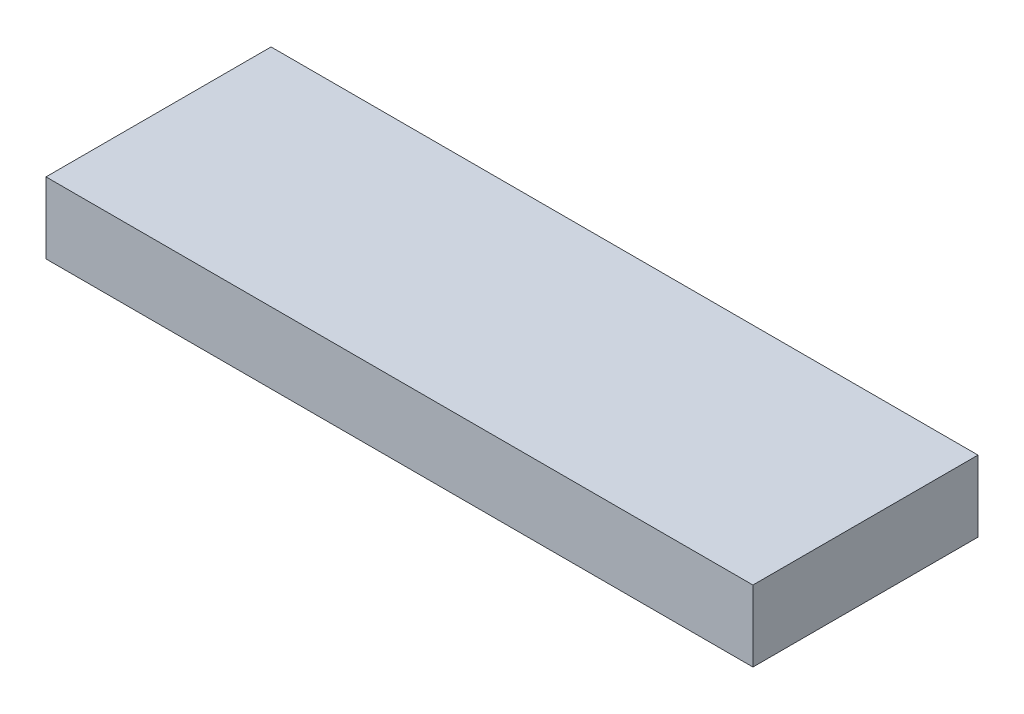
SolidWorks part; units mm, degrees
material "MDF"
ref_plane "Front Plane" through (0, 0, 0) normal (0, 0, 1) x (1, 0, 0)
ref_plane "Top Plane" through (0, 0, 0) normal (0, 1, 0) x (1, 0, 0)
ref_plane "Right Plane" through (0, 0, 0) normal (1, 0, 0) x (0, 0, -1)
sketch "Sketch1" plane through (0, 0, 0) normal (0, 0, 1) x (1, 0, 0)
  line L1 (133.8612, 0) -> (323.3388, 0)
  line L2 (133.8612, 0) -> (133.8612, -19.05)
  line L3 (133.8612, -19.05) -> (323.3388, -19.05)
  line L4 (323.3388, 0) -> (323.3388, -19.05)
  line L5 (323.3388, -298.45) -> (323.3388, 20.8246) construction
  line L6 (133.8612, -298.45) -> (133.8612, 20.8246) construction
  line L8 (456.6888, 0) -> (0.5112, 0) construction
  dimension "D1" = 19.05
extrude "Boss-Extrude1" add sketch "Sketch1" along normal up to surface (60.325 mm away)
hole_wizard "Hole1" positions "Sketch2" profile "Sketch3" legacy
sketch "Sketch2" plane through (228.6, 0, -25.4) normal (0, 0, -1) x (-1, 0, 0)
  line L0 (218.5638, 0) -> (218.5638, -437.642) construction
  line L4 (104.2638, 0) -> (104.2638, -298.45) construction
  line L13 (120.1388, -460.375) -> (120.1388, -311.15) construction
  line L16 (126.4888, -311.15) -> (113.7888, -311.15) construction
  line L18 (126.4888, -304.8) -> (-126.4888, -304.8) construction
  line L22 (94.7388, -276.225) -> (-94.7388, -276.225) construction
  line L24 (-94.7388, -285.75) -> (-94.7388, -266.7) construction
  line L26 (94.7388, -285.75) -> (94.7388, -266.7) construction
  line L27 (-94.7388, 0) -> (-94.7388, -19.05) construction
  line L29 (94.7388, 0) -> (94.7388, -19.05) construction
  line L31 (94.7388, -9.525) -> (-94.7388, -9.525) construction
  point P15 (218.5638, -31.75)
  point P17 (218.5638, -218.821)
  point P19 (218.5638, -418.592)
  point P28 (104.2638, -19.05)
  point P30 (104.2638, -149.225)
  point P32 (104.2638, -279.4)
  point P69 (120.1388, -330.2)
  point P71 (120.1388, -441.325)
  point P76 (-120.1388, -441.325)
  point P77 (-120.1388, -330.2)
  point P80 (-104.2638, -279.4)
  point P81 (-104.2638, -149.225)
  point P82 (-104.2638, -19.05)
  point P83 (-218.5638, -418.592)
  point P84 (-218.5638, -218.821)
  point P85 (-218.5638, -31.75)
  point P99 (0, -304.8)
  point P101 (107.4388, -304.8)
  point P103 (-107.4388, -304.8)
  point P127 (75.6888, -276.225)
  point P129 (0, -276.225)
  point P131 (-75.6888, -276.225)
  point P152 (75.6888, -9.525)
  point P154 (0, -9.525)
  point P156 (-75.6888, -9.525)
  point P158 (0, 0)
sketch "Sketch3" plane through (304.2888, -9.525, -25.4) normal (1, 0, 0) x (0, 1, 0)
  line L0 (0, 0) -> (0, 39.0539)
  line L1 (0, 39.0539) -> (1.5875, 38.1)
  line L2 (1.5875, 38.1) -> (1.5875, 4.0177)
  line L3 (1.5875, 4.0177) -> (5.08, 0)
  line L4 (5.08, 0) -> (0, 0)
  line L5 (0, -14.3089) -> (0, 102.4216) construction
  line L6 (0, 39.0539) -> (-1.5875, 38.1) construction
  line L7 (-1.5875, 4.0177) -> (-5.08, 0) construction
  dimension "Diameter" = 3.175
  dimension "Depth" = 38.1
  dimension "C-Sink Diameter" = 10.16
  dimension "C-Sink Angle" = 82
  dimension "Drill Angle" = 118
